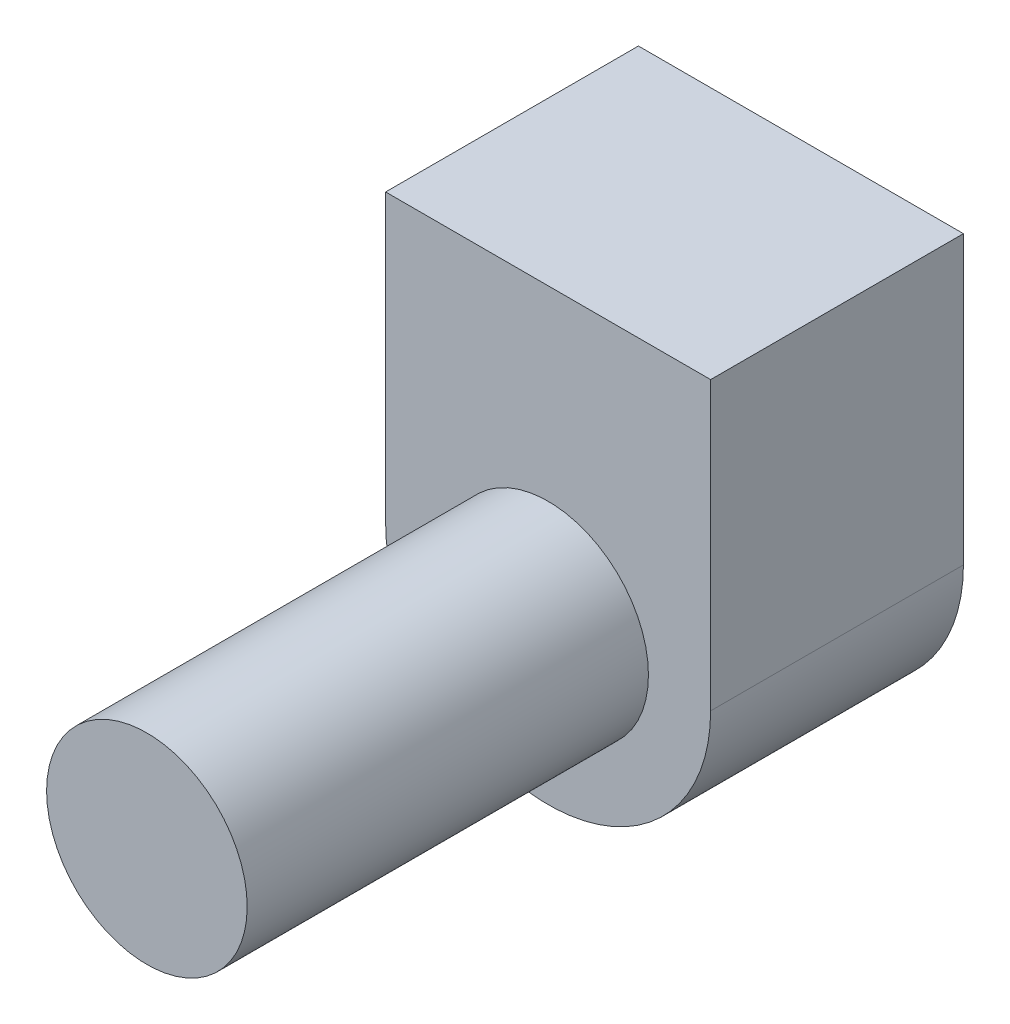
SolidWorks part; units mm, degrees
ref_plane "XY" through (0, 0, 0) normal (0, 0, 1) x (1, 0, 0)
ref_plane "XZ" through (0, 0, 0) normal (0, 1, 0) x (1, 0, 0)
ref_plane "YZ" through (0, 0, 0) normal (1, 0, 0) x (0, 0, -1)
ref_axis "X" through (-11.3157, 0, 0) along (1, 0, 0)
ref_axis "Y" through (0, -25.3365, 0) along (0, 1, 0)
ref_axis "Z" through (0, 0, 8.8011) along (0, 0, -1)
sketch "Sketch1" plane through (0, 0, 0) normal (0, 0, 1) x (1, 0, 0)
  line L0 (-10.287, 0) -> (10.287, 0)
  line L1 (10.287, 0) -> (10.287, -18.161)
  line L2 (-10.287, -18.161) -> (-10.287, 0)
  line L3 (0, 0) -> (0, -18.161) construction
  arc A0 (10.287, -18.161) -> (-10.287, -18.161) centre (0, -18.161) cw
  point P4 (0, 0)
  point P9 (0, -28.448)
  dimension "D1" = 28.448
  dimension "D2" = 20.574
extrude "Boss-Extrude1" add sketch "Sketch1" along normal mid plane 16.002
sketch "Sketch2" plane through (0, 0, 8.001) normal (0, 0, 1) x (1, 0, 0)
  circle A0 centre (0, -18.161) radius 6.35
  arc A1 (-10.287, -18.161) -> (10.287, -18.161) centre (0, -18.161) ccw construction
  dimension "D1" = 12.7
extrude "Boss-Extrude2" add sketch "Sketch2" along normal blind 25.4
